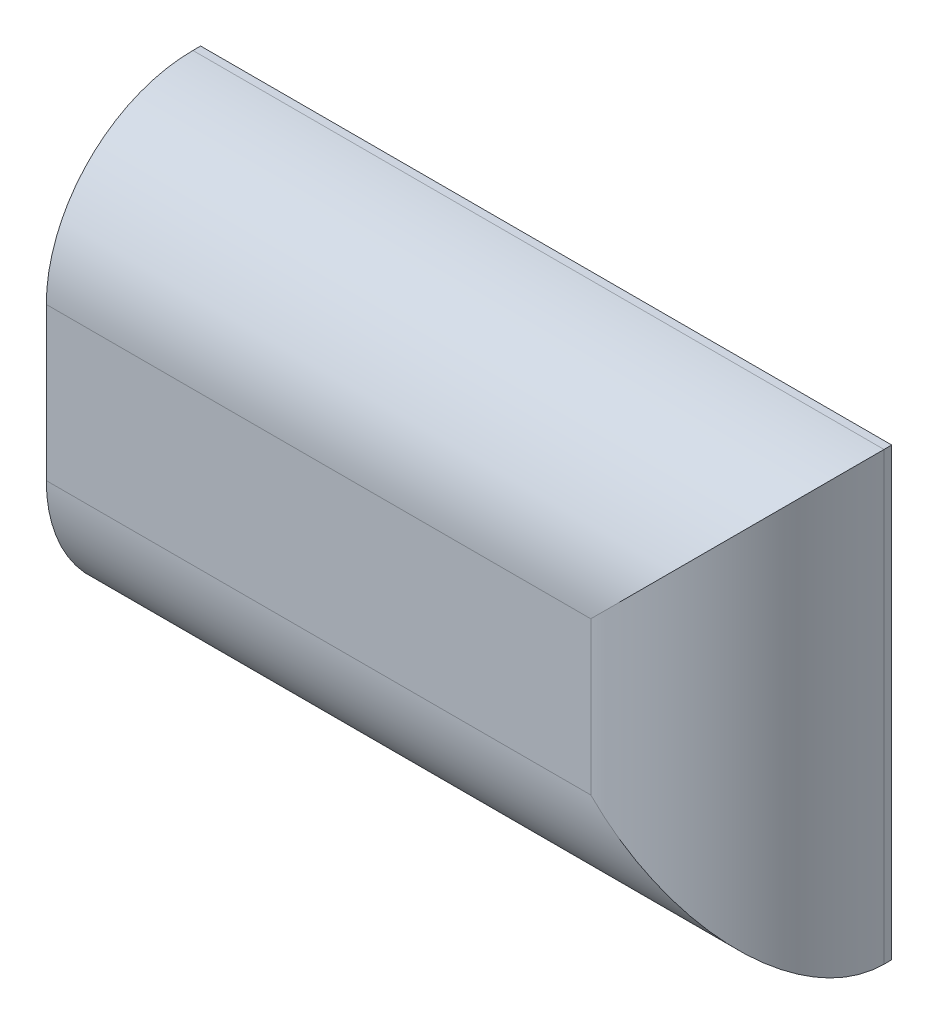
SolidWorks part; units mm, degrees
ref_plane "Front Plane" through (0, 0, 0) normal (0, 0, 1) x (1, 0, 0)
ref_plane "Top Plane" through (0, 0, 0) normal (0, 1, 0) x (1, 0, 0)
ref_plane "Right Plane" through (0, 0, 0) normal (1, 0, 0) x (0, 0, -1)
sketch "Sketch1" plane through (0, 0, 0) normal (0, 0, 1) x (1, 0, 0)
  line L1 (-157.1585, 526.6667) -> (290.6097, 526.6667)
  line L2 (-157.1585, 526.6667) -> (-157.1585, 237.8145)
  line L3 (-157.1585, 237.8145) -> (290.6097, 237.8145)
  line L4 (290.6097, 526.6667) -> (290.6097, 237.8145)
  point P4 (-148.4606, 357.136)
extrude "Boss-Extrude1" add sketch "Sketch1" along normal blind 100
fillet "Fillet1" radius 95 3 edges at (66.7256, 526.6667, 100) (290.6097, 382.2406, 100) (66.7256, 237.8145, 100)
